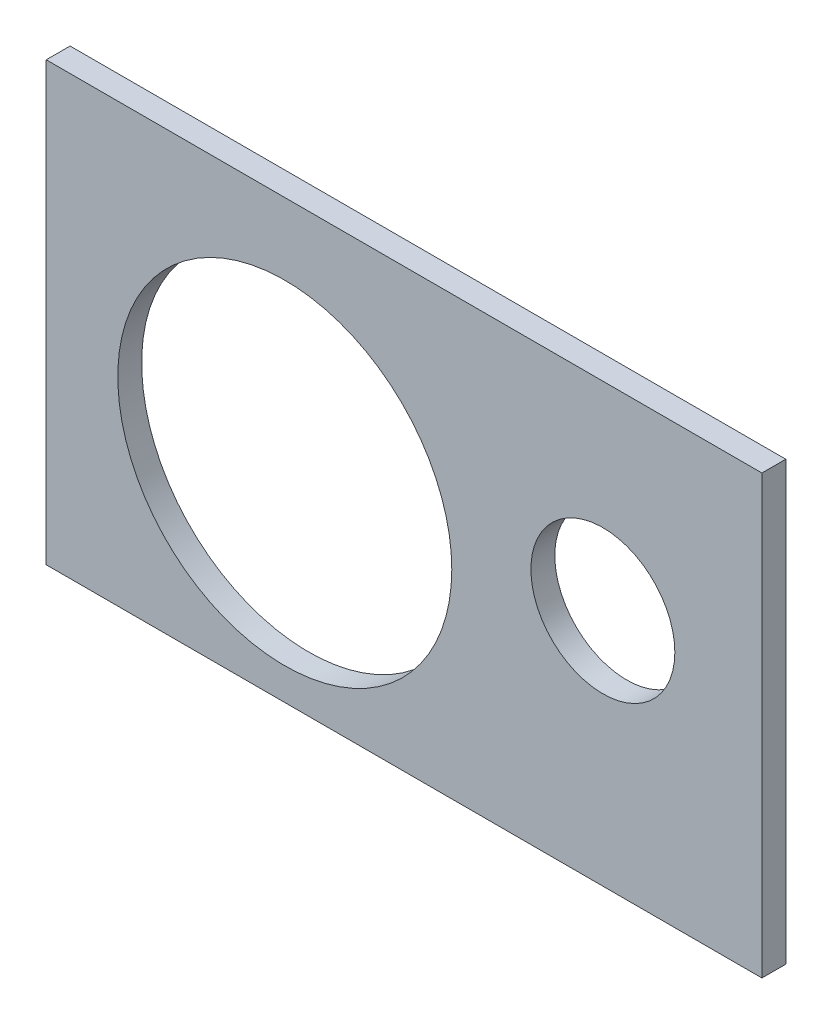
SolidWorks part; units mm, degrees
ref_plane "Front Plane" through (0, 0, 0) normal (0, 0, 1) x (1, 0, 0)
ref_plane "Top Plane" through (0, 0, 0) normal (0, 1, 0) x (1, 0, 0)
ref_plane "Right Plane" through (0, 0, 0) normal (1, 0, 0) x (0, 0, -1)
sketch "Sketch1" plane through (0, 0, 0) normal (0, 0, 1) x (1, 0, 0)
  line L1 (0, 0) -> (180, 0)
  line L2 (0, 0) -> (0, 110)
  line L3 (0, 110) -> (180, 110)
  line L4 (180, 0) -> (180, 110)
  circle A0 centre (60, 50) radius 42
  circle A1 centre (140, 60) radius 18.1
extrude "Boss-Extrude1" add sketch "Sketch1" along normal blind 6
